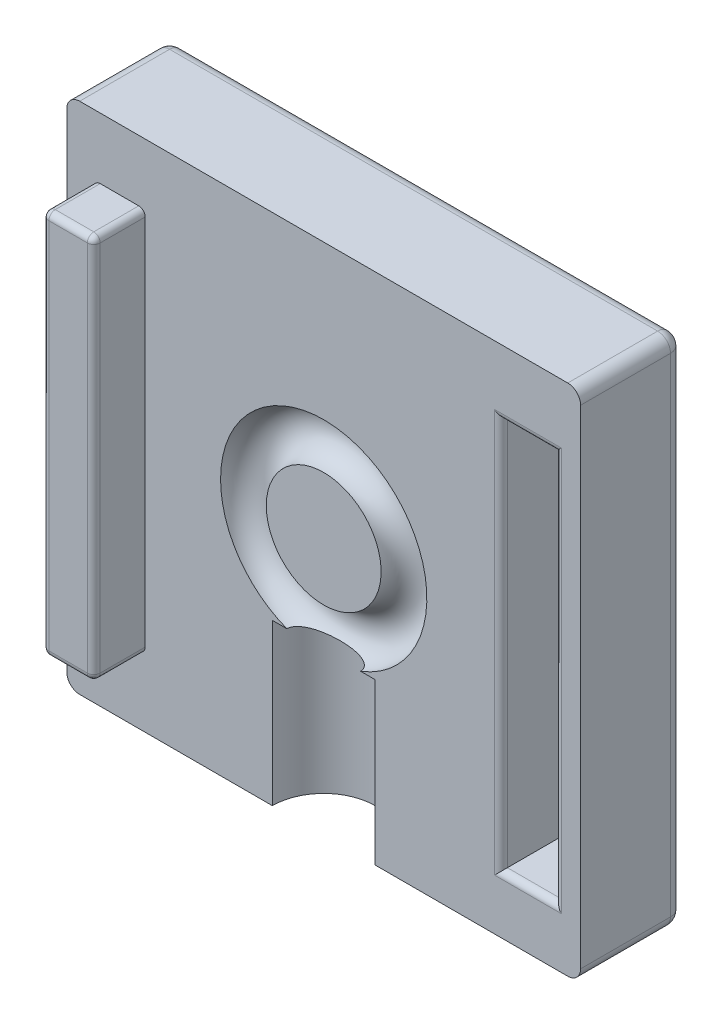
SolidWorks part; units mm, degrees
ref_plane "Front Plane" through (0, 0, 0) normal (0, 0, 1) x (1, 0, 0)
ref_plane "Top Plane" through (0, 0, 0) normal (0, 1, 0) x (1, 0, 0)
ref_plane "Right Plane" through (0, 0, 0) normal (1, 0, 0) x (0, 0, -1)
sketch "Sketch1" plane through (0, 0, 0) normal (0, 0, 1) x (1, 0, 0)
  line L1 (10, -10) -> (-10, -10)
  line L2 (10, -10) -> (10, 10)
  line L3 (10, 10) -> (-10, 10)
  line L4 (-10, -10) -> (-10, 10)
  line L5 (10, -10) -> (-10, 10) construction
  line L6 (10, 10) -> (-10, -10) construction
  point P0 (0, 0)
  dimension "D1" = 20
  dimension "D2" = 20
extrude "Boss-Extrude1" add sketch "Sketch1" along normal blind 4
sketch "Sketch4" plane through (0, 0, 0) normal (0, 1, 0) x (1, 0, 0)
  line L0 (10, -4) -> (-10, -4) construction
  line L1 (0, 0) -> (0, -8.7634) construction
  circle A0 centre (3.125, -4) radius 0.89
  point P7 (2.235, -4)
  point P8 (4.015, -4)
  dimension "D1" = 2.235
  dimension "D2" = 1.78
revolve "Cut-Revolve1" cut sketch "Sketch4" angle 360 about L1
ref_plane "Plane1" through (0, -4, 0) normal (0, 1, 0) x (1, 0, 0)
sketch "Sketch6" plane through (0, -4, 0) normal (0, 1, 0) x (1, 0, 0)
  line L0 (-10, -4) -> (10, -4) construction
  circle A0 centre (0, -4) radius 2
  dimension "D1" = 4
extrude "Cut-Extrude1" cut sketch "Sketch6" against normal blind 8 and the other way blind 0.25
sketch "Sketch7" plane through (0, 0, 4) normal (0, 0, 1) x (1, 0, 0)
  line L0 (-10, 10) -> (-10, -10) construction
  line L1 (-6.95, 7.6214) -> (-8.95, 7.6214)
  line L2 (-6.95, 7.6214) -> (-6.95, -7.3786)
  line L3 (-6.95, -7.3786) -> (-8.95, -7.3786)
  line L4 (-8.95, 7.6214) -> (-8.95, -7.3786)
  line L5 (-6.95, 7.6214) -> (-8.95, -7.3786) construction
  line L6 (-6.95, -7.3786) -> (-8.95, 7.6214) construction
  point P0 (-7.95, 0.1214)
  dimension "D1" = 15
  dimension "D2" = 2
  dimension "D3" = 1.05
extrude "Boss-Extrude2" add sketch "Sketch7" along normal blind 2
sketch "Sketch8" plane through (0, 0, 4) normal (0, 0, 1) x (1, 0, 0)
  line L0 (10, -10) -> (10, 10) construction
  line L1 (9, 7.4342) -> (6.9, 7.4342)
  line L2 (9, 7.4342) -> (9, -7.7658)
  line L3 (9, -7.7658) -> (6.9, -7.7658)
  line L4 (6.9, 7.4342) -> (6.9, -7.7658)
  line L5 (9, 7.4342) -> (6.9, -7.7658) construction
  line L6 (9, -7.7658) -> (6.9, 7.4342) construction
  point P0 (7.95, -0.1658)
  dimension "D1" = 15.2
  dimension "D2" = 2.1
  dimension "D3" = 1
extrude "Cut-Extrude2" cut sketch "Sketch8" against normal blind 2.5
fillet "Fillet1" radius 0.25 4 edges at (-7.95, 7.6214, 6) (-6.95, 0.1214, 6) (-7.95, -7.3786, 6) (-8.95, 0.1214, 6)
fillet "Fillet2" radius 0.25 8 edges at (-7.0232, 7.5482, 5.9268) (-8.8768, 7.5482, 5.9268) (-8.8768, -7.3053, 5.9268) (-7.0232, -7.3053, 5.9268) (-6.95, 7.6214, 4.875) (-8.95, 7.6214, 4.875) (-8.95, -7.3786, 4.875) (-6.95, -7.3786, 4.875)
fillet "Fillet3" radius 0.25 4 edges at (7.95, -7.7658, 4) (9, -0.1658, 4) (7.95, 7.4342, 4) (6.9, -0.1658, 4)
fillet "Fillet5" radius 0.5 4 edges at (0, -10, 0) (10, 0, 0) (0, 10, 0) (-10, 0, 0)
fillet "Fillet6" radius 0.5 8 edges at (-9.8536, -9.8536, 0.1464) (-9.8536, 9.8536, 0.1464) (9.8536, 9.8536, 0.1464) (9.8536, -9.8536, 0.1464) (-10, -10, 2.25) (-10, 10, 2.25) (10, 10, 2.25) (10, -10, 2.25)
